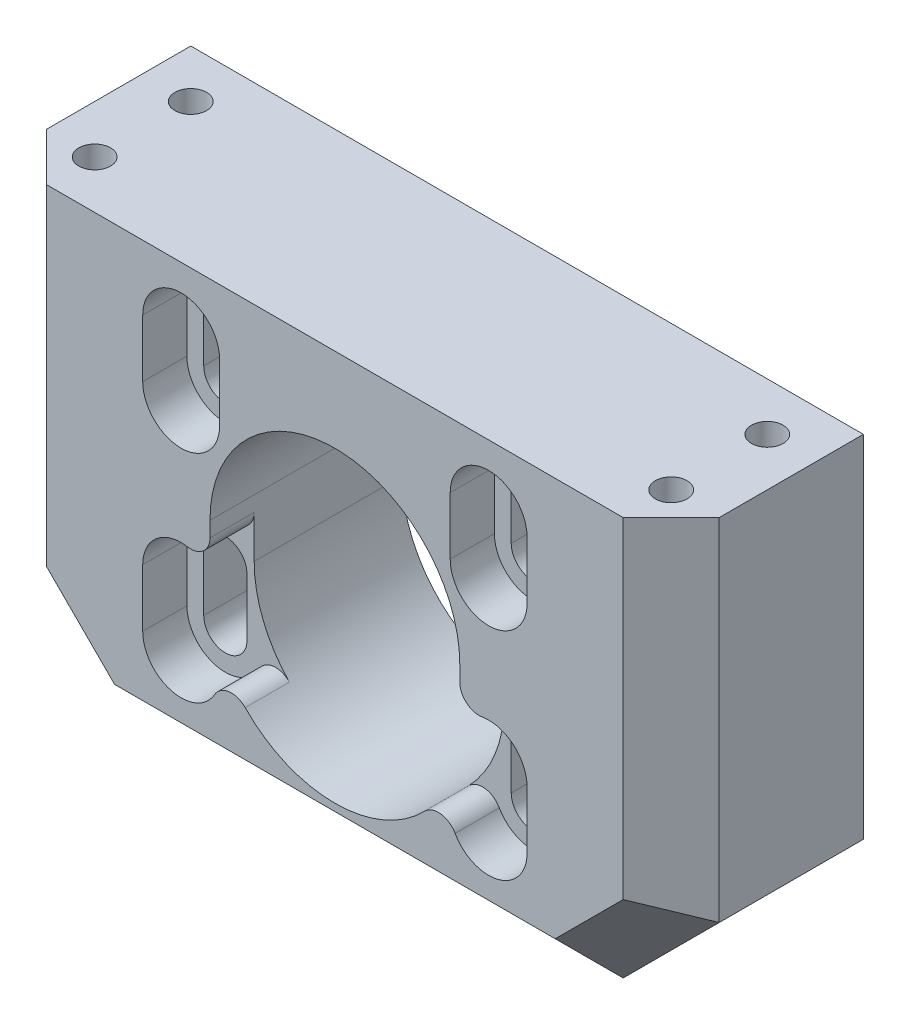
SolidWorks part; units mm, degrees
material "6061 Alloy"
ref_plane "Front Plane" through (0, 0, 0) normal (0, 0, 1) x (1, 0, 0)
ref_plane "Top Plane" through (0, 0, 0) normal (0, 1, 0) x (1, 0, 0)
ref_plane "Right Plane" through (0, 0, 0) normal (1, 0, 0) x (0, 0, -1)
sketch "Sketch1" plane through (0, 0, 0) normal (0, 0, 1) x (1, 0, 0)
  line L5 (35, -23.25) -> (-35, -23.25)
  line L6 (35, -23.25) -> (35, 23.25)
  line L7 (35, 23.25) -> (-35, 23.25)
  line L8 (-35, -23.25) -> (-35, 23.25)
  line L9 (35, -23.25) -> (-35, 23.25) construction
  line L10 (35, 23.25) -> (-35, -23.25) construction
  point P0 (0, 0)
  dimension "D1" = 46.5
  dimension "D2" = 70
extrude "Boss-Extrude1" add sketch "Sketch1" along normal blind 20
sketch "Sketch2" plane through (0, 0, 20) normal (0, 0, 1) x (1, 0, 0)
  line L0 (0, -4.5) -> (0, 1.5) construction
  line L1 (-13, -4.5) -> (-13, 1.5)
  line L2 (13, -4.5) -> (13, 1.5)
  arc A0 (-13, -4.5) -> (13, -4.5) centre (0, -4.5) ccw
  arc A1 (13, 1.5) -> (-13, 1.5) centre (0, 1.5) ccw
  point P2 (0, -1.5)
  dimension "D1" = 13
  dimension "D2" = 1.5
  dimension "D3" = 6
extrude "Cut-Extrude1" cut sketch "Sketch2" against normal through all contours L1 A1 L2 A0
hole_wizard "CBORE for M4 Hexagon socket head cap screws1" positions "Sketch3" profile "Sketch5" counterbore size "M4" standard "GB" end condition through all
sketch "Sketch3" plane through (0, 0, 20) normal (0, 0, 1) x (1, 0, 0)
  line L0 (0, -11) -> (0, 11) construction
  line L1 (-13, 1.5) -> (13, -4.5) construction
  point P0 (-16, 13.5)
  point P2 (-16, -9)
  point P7 (16, -9)
  point P8 (16, 13.5)
  point P22 (0, -1.5)
  dimension "D1" = 32
  dimension "D2" = 7.5
  dimension "D3" = 15
sketch "Sketch5" plane through (-16, 13.5, 20) normal (1, 0, 0) x (0, -1, 0)
  line L0 (0, 0) -> (0, 20)
  line L1 (0, 20) -> (2.25, 20)
  line L3 (2.25, 20) -> (2.25, 4.6)
  line L4 (2.25, 4.6) -> (4, 4.6)
  line L5 (4, 4.6) -> (4, 0)
  line L7 (4, 0) -> (0, 0)
  line L11 (0, -6.35) -> (0, 107.95) construction
  dimension "Thru Hole Dia." = 4.5
  dimension "Thru Hole Depth" = 20
  dimension "C'Bore Dia." = 8
  dimension "C'Bore Depth" = 4.6
sketch "Sketch6" plane through (0, 0, 15.4) normal (0, 0, 1) x (1, 0, 0)
  line L0 (-16, 16.5) -> (-16, 10.5) construction
  line L1 (-12, 16.5) -> (-12, 10.5)
  line L2 (-20, 16.5) -> (-20, 10.5)
  line L3 (-16, -6) -> (-16, -12) construction
  line L4 (-12, -6) -> (-12, -12)
  line L5 (-20, -6) -> (-20, -12)
  line L6 (16, 16.5) -> (16, 10.5) construction
  line L7 (20, 16.5) -> (20, 10.5)
  line L8 (12, 16.5) -> (12, 10.5)
  line L9 (16, -12) -> (16, -6) construction
  line L10 (12, -12) -> (12, -6)
  line L11 (20, -12) -> (20, -6)
  arc A0 (-12, 16.5) -> (-20, 16.5) centre (-16, 16.5) ccw
  arc A1 (-20, 10.5) -> (-12, 10.5) centre (-16, 10.5) ccw
  circle A3 centre (-16, 13.5) radius 4 construction
  arc A4 (-12, -6) -> (-20, -6) centre (-16, -6) ccw
  arc A5 (-20, -12) -> (-12, -12) centre (-16, -12) ccw
  arc A7 (20, 16.5) -> (12, 16.5) centre (16, 16.5) ccw
  arc A8 (12, 10.5) -> (20, 10.5) centre (16, 10.5) ccw
  arc A9 (12, -12) -> (20, -12) centre (16, -12) ccw
  arc A10 (20, -6) -> (12, -6) centre (16, -6) ccw
  point P2 (-16, 13.5)
  point P10 (-16, -9)
  point P20 (16, 13.5)
  point P28 (16, -9)
  dimension "D1" = 6
extrude "Cut-Extrude2" cut sketch "Sketch6" along normal through all
sketch "Sketch7" plane through (0, 0, 15.4) normal (0, 0, 1) x (1, 0, 0)
  line L0 (-16, 16.5) -> (-16, 10.5) construction
  line L1 (-13.75, 16.5) -> (-13.75, 10.5)
  line L2 (-18.25, 16.5) -> (-18.25, 10.5)
  line L3 (-16, -12) -> (-16, -6) construction
  line L4 (-18.25, -12) -> (-18.25, -6)
  line L5 (-13.75, -12) -> (-13.75, -6)
  line L6 (16, 16.5) -> (16, 10.5) construction
  line L7 (18.25, 16.5) -> (18.25, 10.5)
  line L8 (13.75, 16.5) -> (13.75, 10.5)
  line L9 (16, -6) -> (16, -12) construction
  line L10 (18.25, -6) -> (18.25, -12)
  line L11 (13.75, -6) -> (13.75, -12)
  arc A0 (-13.75, 16.5) -> (-18.25, 16.5) centre (-16, 16.5) ccw
  arc A1 (-18.25, 10.5) -> (-13.75, 10.5) centre (-16, 10.5) ccw
  arc A2 (-18.25, -12) -> (-13.75, -12) centre (-16, -12) ccw
  arc A3 (-13.75, -6) -> (-18.25, -6) centre (-16, -6) ccw
  arc A4 (18.25, 16.5) -> (13.75, 16.5) centre (16, 16.5) ccw
  arc A5 (13.75, 10.5) -> (18.25, 10.5) centre (16, 10.5) ccw
  arc A6 (18.25, -6) -> (13.75, -6) centre (16, -6) ccw
  arc A7 (13.75, -12) -> (18.25, -12) centre (16, -12) ccw
  arc A8 (-12, 16.5) -> (-20, 16.5) centre (-16, 16.5) ccw construction
  circle A9 centre (-16, 13.5) radius 2.25 construction
  point P2 (-16, 13.5)
  point P9 (-16, -9)
  point P17 (16, 13.5)
  point P25 (16, -9)
extrude "Cut-Extrude3" cut sketch "Sketch7" against normal through all
fillet "Fillet1" radius 2 4 edges at (13, -3.3542, 17.7) (12, -9.5, 17.7) (-12, -9.5, 17.7) (-13, -3.3542, 17.7)
chamfer "Chamfer1" distance 10 angle 45 2 edges at (35, -23.25, 10) (-35, -23.25, 10)
hole_wizard "M4 Tapped Hole1" positions "Sketch9" profile "Sketch11" tap size "M4" standard "GB"
sketch "Sketch9" plane through (0, 23.25, 0) normal (0, 1, 0) x (1, 0, 0)
  line L0 (0, -11) -> (0, 11) construction
  line L1 (-35, -20) -> (-35, 0) construction
  line L2 (35, 0) -> (-35, 0) construction
  line L3 (35, -20) -> (-35, -20) construction
  point P0 (-30, -15)
  point P6 (-30, -5)
  point P12 (30, -5)
  point P13 (30, -15)
  dimension "D1" = 5
  dimension "D2" = 5
  dimension "D3" = 5
cosmetic thread "Hole Thread1" parameters "D1"=8, "D2"=4
cosmetic thread "Hole Thread2" parameters "D1"=8, "D2"=4
cosmetic thread "Hole Thread3" parameters "D1"=8, "D2"=4
cosmetic thread "Hole Thread4" parameters "D1"=8, "D2"=4
sketch "Sketch11" plane through (-30, 23.25, 15) normal (1, 0, 0) x (0, 0, 1)
  line L0 (0, 0) -> (0, 10.9914)
  line L1 (0, 10.9914) -> (1.65, 10)
  line L2 (1.65, 10) -> (1.65, 0)
  line L5 (1.65, 0) -> (0, 0)
  line L10 (0, 10.9914) -> (-1.65, 10) construction
  line L11 (0, -6.35) -> (0, 107.95) construction
  dimension "Tap Drill Dia." = 3.3
  dimension "Tap Drill Depth" = 10
  dimension "Drill Angle" = 118
chamfer "Chamfer2" distance 5 angle 45 5 edges at (35, 5, 20) (-35, 5, 20) (30, -18.25, 20) (0, -23.25, 20) (-30, -18.25, 20)
